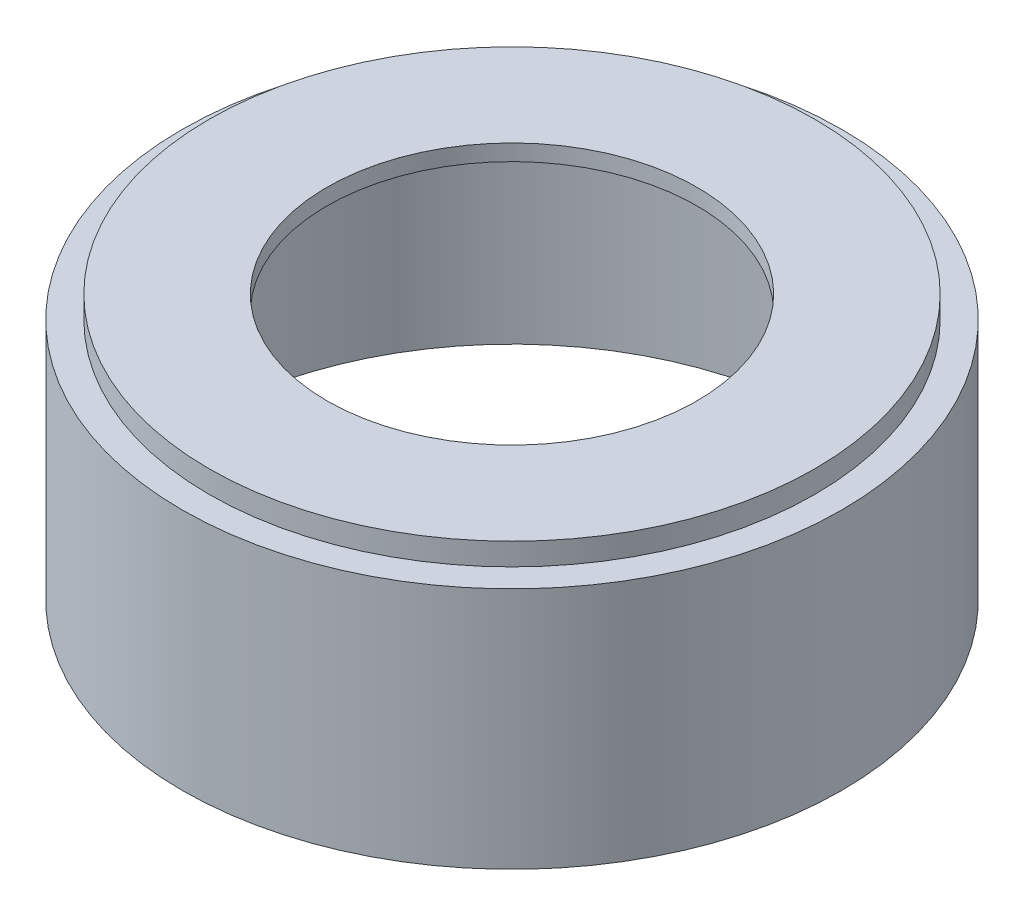
SolidWorks part; units mm, degrees
ref_plane "Front Plane" through (0, 0, 0) normal (0, 0, 1) x (1, 0, 0)
ref_plane "Top Plane" through (0, 0, 0) normal (0, 1, 0) x (1, 0, 0)
ref_plane "Right Plane" through (0, 0, 0) normal (1, 0, 0) x (0, 0, -1)
sketch "Sketch1" plane through (0, 0, 0) normal (0, 1, 0) x (1, 0, 0)
  circle A0 centre (0, 0) radius 24.5
  dimension "D1" = 49
extrude "Boss-Extrude1" add sketch "Sketch1" along normal blind 19.7
sketch "Sketch2" plane through (0, 19.7, 0) normal (0, 1, 0) x (1, 0, 0)
  circle A0 centre (0, 0) radius 22.5
  circle A1 centre (0, 0) radius 24.5 construction
  circle A2 centre (0, 0) radius 24.5
  dimension "D1" = 45
extrude "Cut-Extrude1" cut sketch "Sketch2" against normal blind 1.65
sketch "Sketch3" plane through (0, 19.7, 0) normal (0, 1, 0) x (1, 0, 0)
  circle A0 centre (0, 0) radius 13.75
  dimension "D1" = 27.5
shell "Shell1" thickness 1.2 removed face at (0, 0, 24.5)
extrude "Cut-Extrude2" cut sketch "Sketch3" against normal up to surface (1.2 mm away) up to face at (0, 18.5, 21.3)
